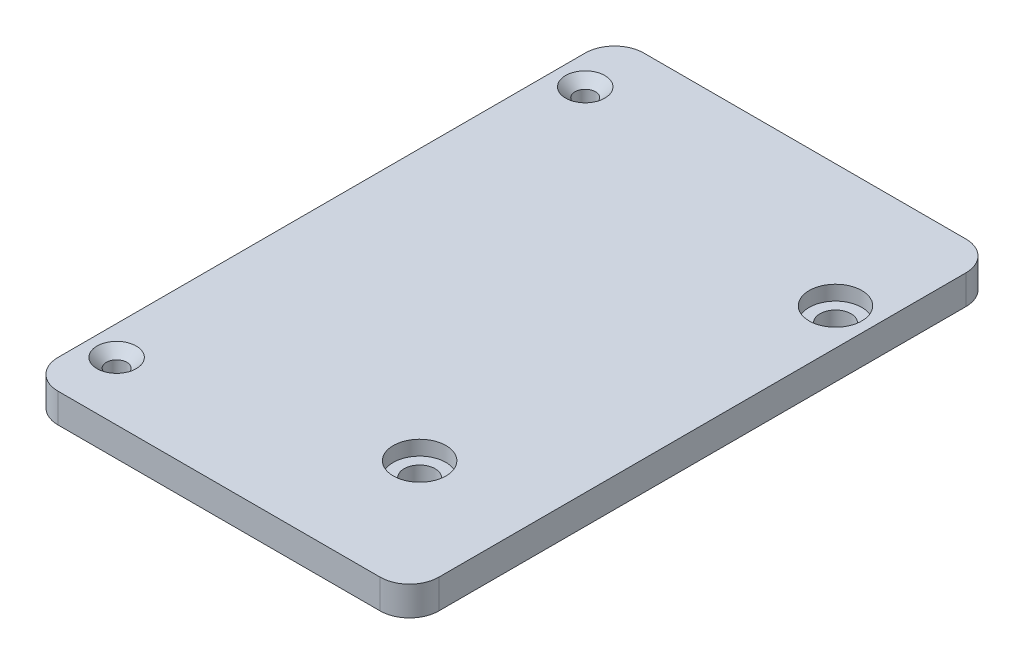
SolidWorks part; units mm, degrees
ref_plane "Front Plane" through (0, 0, 0) normal (0, 0, 1) x (1, 0, 0)
ref_plane "Top Plane" through (0, 0, 0) normal (0, 1, 0) x (1, 0, 0)
ref_plane "Right Plane" through (0, 0, 0) normal (1, 0, 0) x (0, 0, -1)
sketch "Sketch2" plane through (0, 0, 0) normal (0, 1, 0) x (1, 0, 0)
  line L1 (-32.5, 50) -> (32.5, 50)
  line L2 (-32.5, 50) -> (-32.5, -50)
  line L3 (-32.5, -50) -> (32.5, -50)
  line L4 (32.5, 50) -> (32.5, -50)
  line L5 (-32.5, 50) -> (32.5, -50) construction
  line L6 (-32.5, -50) -> (32.5, 50) construction
  circle A0 centre (-27.5, 40) radius 1.75
  circle A1 centre (-27.5, -40) radius 1.75
  circle A2 centre (26.23, 29) radius 2.65
  circle A3 centre (13.65, -29.42) radius 2.65
  point P0 (0, 0)
  dimension "D3" = 3.5
  dimension "D4" = 5
  dimension "D8" = 5.3
  dimension "D9" = 5.3
  dimension "D1" = 65
  dimension "D2" = 100
  dimension "D5" = 5
  dimension "D6" = 10
  dimension "D7" = 10
  dimension "D10" = 18.85
  dimension "D11" = 20.58
  dimension "D12" = 6.27
  dimension "D13" = 21
extrude "Boss-Extrude1" add sketch "Sketch2" along normal blind 5
sketch "Sketch3" plane through (0, 5, 0) normal (0, 1, 0) x (1, 0, 0)
  circle A0 centre (26.23, 29) radius 4.5
  circle A1 centre (13.65, -29.42) radius 4.5
  dimension "D1" = 9
  dimension "D2" = 9
extrude "Cut-Extrude1" cut sketch "Sketch3" against normal blind 2.5
fillet "Fillet1" radius 5 4 edges at (32.5, 2.5, 50) (-32.5, 2.5, -50) (32.5, 2.5, -50) (-32.5, 2.5, 50)
chamfer "Chamfer1" distance 1.6 angle 45 2 edges at (-27.5, 5, 41.75) (-27.5, 5, -38.25)
